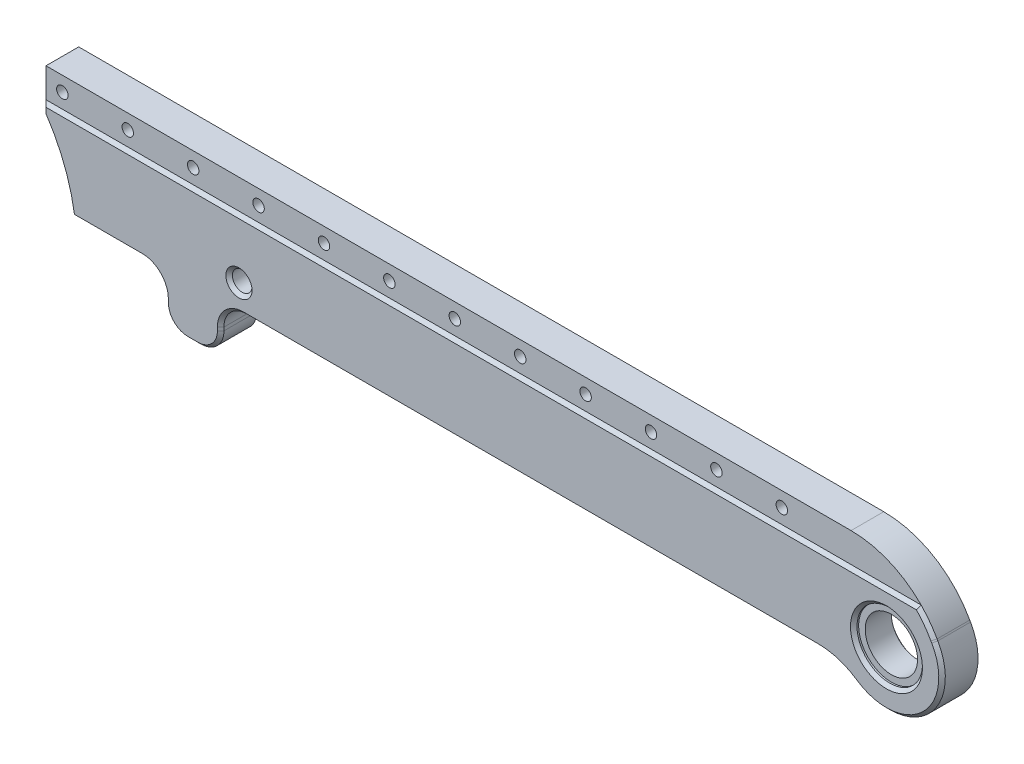
SolidWorks part; units mm, degrees
ref_plane "Front Plane" through (0, 0, 0) normal (0, 0, 1) x (1, 0, 0)
ref_plane "Top Plane" through (0, 0, 0) normal (0, 1, 0) x (1, 0, 0)
ref_plane "Right Plane" through (0, 0, 0) normal (1, 0, 0) x (0, 0, -1)
sketch "Sketch1" plane through (0, 0, 0) normal (0, 0, 1) x (1, 0, 0)
  line L0 (-135, 0) -> (135, 0)
  line L1 (135, 0) -> (135, -35)
  line L2 (135, -35) -> (-135, -35)
  line L3 (-135, -35) -> (-135, 0)
  dimension "D1" = 270
  dimension "D2" = 35
extrude "Boss-Extrude1" add sketch "Sketch1" along normal blind 10
sketch "Sketch2" plane through (0, 0, 10) normal (0, 0, 1) x (1, 0, 0)
  line L0 (135, -35) -> (135, 0) construction
  line L1 (-135, -35) -> (135, -35)
  line L2 (-135, -35) -> (-135, -9)
  line L3 (-135, -9) -> (135, -9)
  line L4 (135, -35) -> (135, -9)
  line L5 (135, 0) -> (-135, 0) construction
  dimension "D1" = 9
extrude "Boss-Extrude2" add sketch "Sketch2" along normal blind 1
sketch "Sketch3" plane through (0, 0, 10) normal (0, 0, 1) x (1, 0, 0)
  line L0 (-135, 0) -> (-135, -9) construction
  circle A0 centre (-130, -4.5) radius 1.75
  circle A1 centre (-110, -4.5) radius 1.75
  circle A2 centre (-90, -4.5) radius 1.75
  circle A3 centre (-70, -4.5) radius 1.75
  circle A4 centre (-50, -4.5) radius 1.75
  circle A5 centre (-30, -4.5) radius 1.75
  circle A6 centre (-10, -4.5) radius 1.75
  circle A7 centre (10, -4.5) radius 1.75
  circle A8 centre (30, -4.5) radius 1.75
  circle A9 centre (50, -4.5) radius 1.75
  circle A10 centre (70, -4.5) radius 1.75
  circle A11 centre (90, -4.5) radius 1.75
  point P4 (-135, -4.5)
  dimension "D1" = 3.5
  dimension "D4" = 20
  dimension "D2" = 5
  dimension "D3" = 12
extrude "Cut-Extrude1" cut sketch "Sketch3" against normal up to next
sketch "Sketch4" plane through (0, 0, 11) normal (0, 0, 1) x (1, 0, 0)
  line L0 (135, -35) -> (135, -9) construction
  line L1 (-135, 0) -> (-135, -9) construction
  circle A0 centre (123, -24.5) radius 8
  point P7 (-135, -4.5)
  dimension "D1" = 16
  dimension "D2" = 12
  dimension "D3" = 20
extrude "Cut-Extrude3" cut sketch "Sketch4" against normal up to next
sketch "Sketch5" plane through (0, 0, 11) normal (0, 0, 1) x (1, 0, 0)
  circle A0 centre (123, -24.5) radius 10
  dimension "D1" = 20
extrude "Cut-Extrude4" cut sketch "Sketch5" against normal blind 1.5
sketch "Sketch6" plane through (0, 0, 0) normal (0, 0, -1) x (-1, 0, 0)
  circle A0 centre (-123, -24.5) radius 10
  dimension "D1" = 20
extrude "Cut-Extrude5" cut sketch "Sketch6" against normal blind 1.5
sketch "Sketch19" plane through (0, 0, 11) normal (0, 0, 1) x (1, 0, 0)
  line L1 (-135, -35) -> (135, -35) construction
  line L2 (-135, -9) -> (-135, -35) construction
  line L3 (-135, -12) -> (-135, -35)
  line L4 (-135, -35) -> (-126.1576, -35)
  arc A0 (-135, -12) -> (-126.1576, -35) centre (-180, -42.5) cw
  dimension "D3" = 54.3622
  dimension "D1" = 8.8424
  dimension "D2" = 3
extrude "Cut-Extrude14" cut sketch "Sketch19" against normal up to next
sketch "Sketch20" plane through (0, 0, 11) normal (0, 0, 1) x (1, 0, 0)
  line L0 (-126.1576, -35) -> (135, -35) construction
  line L1 (-97.5876, -35) -> (-80.5876, -35)
  line L2 (-97.5876, -35) -> (-97.5876, -50)
  line L3 (-97.5876, -50) -> (-80.5876, -50)
  line L4 (-80.5876, -35) -> (-80.5876, -50)
  dimension "D1" = 45.57
  dimension "D2" = 17
  dimension "D3" = 15
extrude "Boss-Extrude5" add sketch "Sketch20" against normal up to surface (11 mm away) up to face at (-24.9675, -16.2985, 0)
sketch "Sketch21" plane through (0, 0, 0) normal (0, 0, -1) x (-1, 0, 0)
  line L1 (80.5876, -35) -> (-135, -35) construction
  line L4 (80.5876, -50) -> (80.5876, -35) construction
  circle A0 centre (89.0876, -41) radius 4.25
  dimension "D1" = 8.5
  dimension "D2" = 8.5
  dimension "D3" = 6
extrude "Cut-Extrude15" cut sketch "Sketch21" against normal offset from surface (9 mm away) 2 up to face at (133, -24.5, 11)
fillet "Fillet1" radius 7 4 edges at (-97.5876, -35, 5.5) (-97.5876, -50, 5.5) (-80.5876, -50, 5.5) (-80.5876, -35, 5.5)
sketch "Sketch22" plane through (0, 0, 11) normal (0, 0, 1) x (1, 0, 0)
  line L0 (-135, -9) -> (-135, -12) construction
  line L1 (-126.1576, -35) -> (-104.5876, -35) construction
  circle A0 centre (-75, -27) radius 1.75
  dimension "D1" = 3.5
  dimension "D2" = 60
  dimension "D3" = 8
extrude "Cut-Extrude16" cut sketch "Sketch22" against normal up to next
sketch "Sketch24" plane through (0, 0, 11) normal (0, 0, 1) x (1, 0, 0)
  circle A0 centre (-75, -27) radius 3
  dimension "D1" = 6
extrude "Cut-Extrude17" cut sketch "Sketch24" against normal blind 5
sketch "Sketch25" plane through (0, 0, 11) normal (0, 0, 1) x (1, 0, 0)
  line L0 (-73.5876, -35) -> (135, -35) construction
  line L2 (135, -35) -> (135, -9) construction
  line L3 (109.6303, -35) -> (135, -35)
  line L4 (135, -35) -> (135, -12.4584)
  arc A0 (109.6303, -35) -> (135, -12.4584) centre (123, -24.5) ccw
  circle A4 centre (123, -24.5) radius 10 construction
  dimension "D1" = 17
extrude "Boss-Extrude6" add sketch "Sketch25" against normal up to surface (11 mm away) up to face at (-76.75, -27, 0)
fillet "Fillet2" radius 20 2 edges at (109.6303, -35, 5.5) (135, -12.4584, 5.5)
fillet "Fillet3" radius 30 1 edges at (135, 0, 5)
chamfer "Chamfer1" distance 1 angle 45 17 edges at (133, -24.5, 11) (-72, -27, 11) (134.5562, -36.9681, 11) (107.9811, -35.8986, 11) (14.233, -35, 11) (-78.5374, -37.0503, 11) (-80.5876, -42.5, 11) (-82.6379, -47.9497, 11) (-89.0876, -50, 11) (-95.5374, -47.9497, 11) (-97.5876, -42.5, 11) (-99.6379, -37.0503, 11) (-129.2585, -22.9924, 11) (-135, -10.5, 11) (-1.1992, -9, 11) (135.2603, -12.1113, 11) (137.5856, -15.7614, 11)
